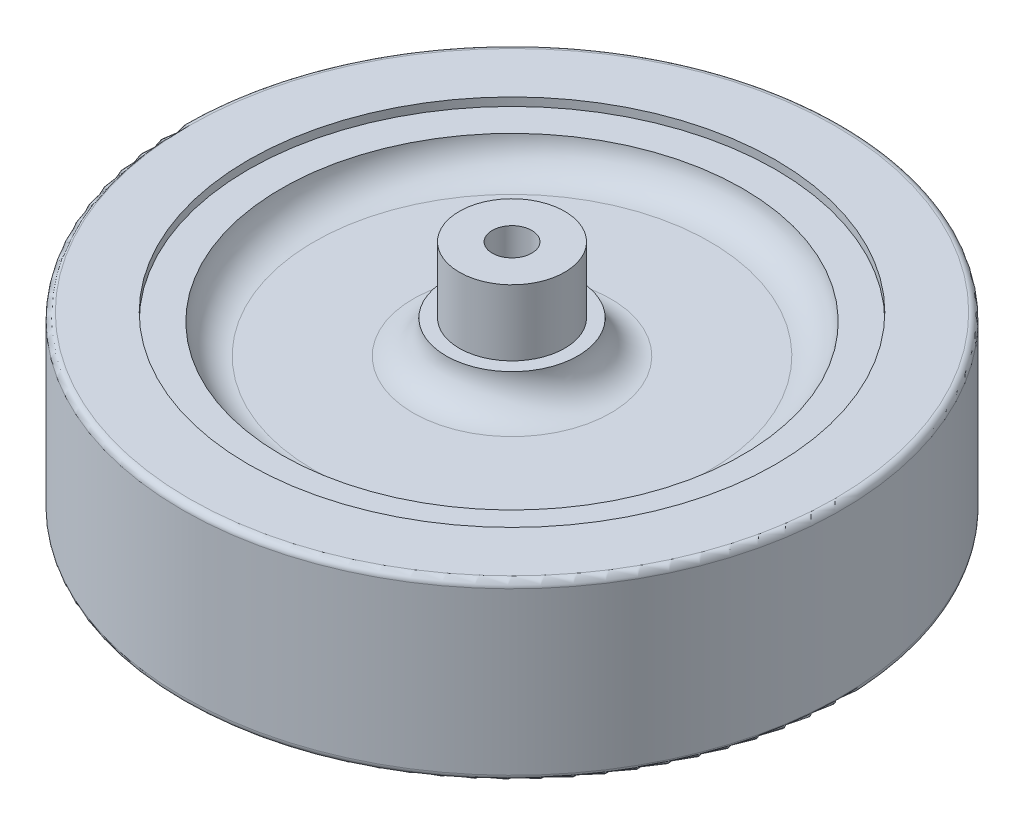
SolidWorks part; units mm, degrees
ref_plane "Front Plane" through (0, 0, 0) normal (0, 0, 1) x (1, 0, 0)
ref_plane "Top Plane" through (0, 0, 0) normal (0, 1, 0) x (1, 0, 0)
ref_plane "Right Plane" through (0, 0, 0) normal (1, 0, 0) x (0, 0, -1)
sketch "Sketch1" plane through (0, 0, 0) normal (0, 1, 0) x (1, 0, 0)
  circle A0 centre (0, 0) radius 50
  circle A1 centre (0, 0) radius 40
extrude "Boss-Extrude1" add sketch "Sketch1" along normal mid plane 26.5
sketch "Sketch2" plane through (0, 0, 0) normal (0, 1, 0) x (1, 0, 0)
  circle A0 centre (0, 0) radius 40
  circle A1 centre (0, 0) radius 35
  circle A2 centre (0, 0) radius 40 construction
extrude "Boss-Extrude2" add sketch "Sketch2" along normal mid plane 24
sketch "Sketch4" plane through (0, 0, 0) normal (0, 1, 0) x (1, 0, 0)
  circle A0 centre (0, 0) radius 35
  circle A2 centre (0, 0) radius 10
extrude "Boss-Extrude3" add sketch "Sketch4" along normal mid plane 15
sketch "Sketch7" plane through (0, 0, 0) normal (0, 1, 0) x (1, 0, 0)
  circle A0 centre (0, 0) radius 10
  circle A4 centre (0, 0) radius 10 construction
extrude "Boss-Extrude4" add sketch "Sketch7" along normal mid plane 25 contours A0
fillet "Fillet1" radius 5 4 edges at (0, -7.5, 35) (0, -7.5, 10) (0, 7.5, 10) (0, 7.5, 35)
sketch "Sketch10" plane through (0, 12.5, 0) normal (0, 1, 0) x (1, 0, 0)
  circle A0 centre (0, 0) radius 8
sketch "Sketch11" plane through (0, 12.5, 0) normal (0, 1, 0) x (1, 0, 0)
  circle A0 centre (0, 0) radius 3
extrude "Boss-Extrude5" add sketch "Sketch10" along normal blind 10
extrude "Cut-Extrude2" cut sketch "Sketch11" along normal through all contours A0
fillet "Fillet2" radius 1 2 edges at (0, -13.25, 50) (0, 13.25, 50)
